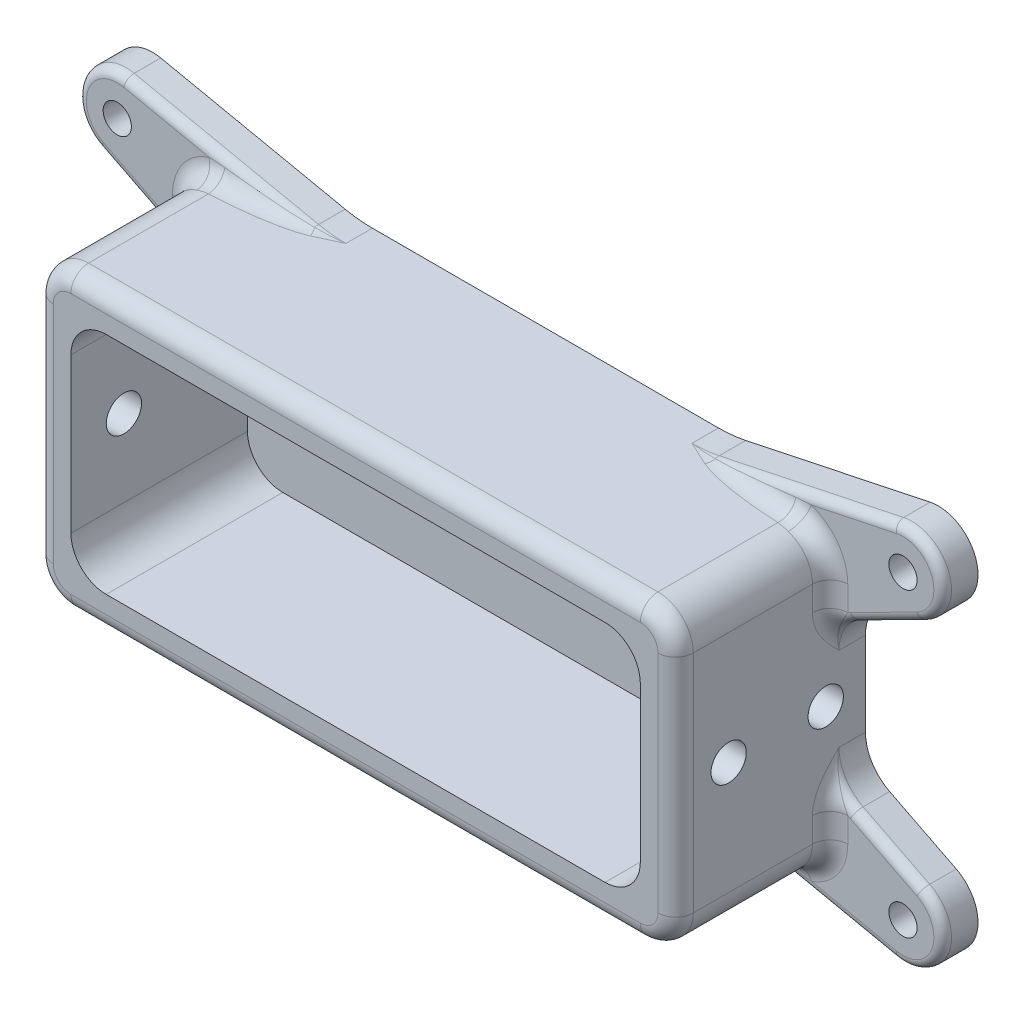
SolidWorks part; units mm, degrees
ref_plane "Спереди" through (0, 0, 0) normal (0, 0, 1) x (1, 0, 0)
ref_plane "Сверху" through (0, 0, 0) normal (0, 1, 0) x (1, 0, 0)
ref_plane "Справа" through (0, 0, 0) normal (1, 0, 0) x (0, 0, -1)
sketch "Эскиз1" plane through (0, 0, 0) normal (0, 0, 1) x (1, 0, 0)
  line L0 (0, 0) -> (50000, 0) construction
  line L1 (0, 0) -> (0, 50000) construction
  line L2 (-43.5744, 21.4603) -> (-21.1628, 16.75)
  line L3 (32.25, -12.75) -> (-32.25, -12.75)
  line L4 (32.25, -12.75) -> (32.25, 12.75)
  line L5 (32.25, 12.75) -> (-32.25, 12.75)
  line L6 (-32.25, -12.75) -> (-32.25, 12.75)
  line L7 (32.25, -12.75) -> (-32.25, 12.75) construction
  line L8 (32.25, 12.75) -> (-32.25, -12.75) construction
  line L9 (-21.1628, 16.75) -> (21.1628, 16.75)
  line L12 (-46.5338, 13.0423) -> (-36.25, 7.832)
  line L13 (-36.25, 7.832) -> (-36.25, -7.832)
  line L14 (-44.5, 17.0565) -> (-32.25, 12.75) construction
  line L15 (-21.1628, -16.75) -> (21.1628, -16.75)
  line L16 (-43.5744, -21.4603) -> (-21.1628, -16.75)
  line L17 (-46.5338, -13.0423) -> (-36.25, -7.832)
  line L18 (43.5744, 21.4603) -> (21.1628, 16.75)
  line L19 (46.5338, 13.0423) -> (36.25, 7.832)
  line L20 (36.25, 7.832) -> (36.25, -7.832)
  line L21 (46.5338, -13.0423) -> (36.25, -7.832)
  line L22 (43.5744, -21.4603) -> (21.1628, -16.75)
  line L23 (-36.25, 7.832) -> (-36.25, 16.75)
  line L24 (-36.25, 16.75) -> (-21.1628, 16.75)
  line L25 (-36.25, -7.832) -> (-36.25, -16.75)
  line L26 (-36.25, -16.75) -> (-21.1628, -16.75)
  line L27 (36.25, 7.832) -> (36.25, 16.75)
  line L28 (36.25, 16.75) -> (21.1628, 16.75)
  line L29 (36.25, -7.832) -> (36.25, -16.75)
  line L30 (36.25, -16.75) -> (21.1628, -16.75)
  circle A0 centre (-44.5, 17.0565) radius 1.6
  circle A1 centre (-44.5, -17.0565) radius 1.6
  circle A2 centre (44.5, 17.0565) radius 1.6
  circle A3 centre (44.5, -17.0565) radius 1.6
  arc A4 (-43.5744, 21.4603) -> (-46.5338, 13.0423) centre (-44.5, 17.0565) ccw
  arc A5 (-43.5744, -21.4603) -> (-46.5338, -13.0423) centre (-44.5, -17.0565) cw
  arc A6 (43.5744, 21.4603) -> (46.5338, 13.0423) centre (44.5, 17.0565) cw
  arc A7 (43.5744, -21.4603) -> (46.5338, -13.0423) centre (44.5, -17.0565) ccw
  point P14 (0, 0)
  dimension "D1" = 3.2
  dimension "D2" = 64.5
  dimension "D3" = 25.5
  dimension "D4" = 4
  dimension "D5" = 4
  dimension "D6" = 15
extrude "Бобышка-Вытянуть1" add sketch "Эскиз1" along normal blind 1.5 contours L22 A7 L21 L20 L19 A6 L18 L9 L2 A4 L12 L13 L17 A5 L16 L15 A2 L3 L6 L5 L4 A0 A1 A3 | L6 L3 L4 L5 | L2 A4 L12 L23 L24 A0 | A5 L16 L26 L25 L17 A1 | L22 A7 L21 L29 L30 A3 | A6 L18 L28 L27 L19 A2 region at (-39.8492, 16.0291, 0) region at (0, 15.9513, 0) region at (39.8492, 16.0291, 0) region at (-39.8492, -16.0291, 0) region at (39.8492, -16.0291, 0) region at (0, 0, 0)
extrude "Бобышка-Вытянуть2" add sketch "Эскиз1<3>" along normal blind 4 contours L22 A7 L21 L20 L19 A6 L18 L9 L2 A4 L12 L13 L17 A5 L16 L15 A2 L3 L6 L5 L4 A0 A1 A3 | L2 A4 L12 L23 L24 A0 | A5 L16 L26 L25 L17 A1 | L22 A7 L21 L29 L30 A3 | A6 L18 L28 L27 L19 A2 region at (-39.8492, 16.0291, 0) region at (0, 15.9513, 0) region at (39.8492, 16.0291, 0) region at (-39.8492, -16.0291, 0) region at (39.8492, -16.0291, 0)
sketch "Эскиз1<3>" plane through (0, 0, 0) normal (0, 0, 1) x (1, 0, 0) same geometry as "Эскиз1"
extrude "Бобышка-Вытянуть4" add sketch "Эскиз1<4>" along normal blind 20 from surface contours L30 L29 L20 L27 L28 L9 L24 L23 L13 L25 L26 L15 L3 L6 L5 L4 region at (0, 15.9513, 0) starting at face at (0, 0, 1.5)
sketch "Эскиз1<4>" plane through (0, 0, 0) normal (0, 0, 1) x (1, 0, 0) same geometry as "Эскиз1"
fillet "Скругление1" radius 15 4 edges at (21.1628, 16.75, 2) (-21.1628, 16.75, 2) (21.1628, -16.75, 2) (-21.1628, -16.75, 2)
fillet "Скругление2" radius 5 4 edges at (36.25, 7.832, 2) (36.25, -7.832, 2) (-36.25, -7.832, 2) (-36.25, 7.832, 2)
fillet "Скругление4" radius 4 8 edges at (-32.25, -12.75, 11.5) (-32.25, 12.75, 11.5) (32.25, 12.75, 11.5) (32.25, -12.75, 11.5) (36.25, -16.75, 12.75) (-36.25, -16.75, 12.75) (-36.25, 16.75, 12.75) (36.25, 16.75, 12.75)
fillet "Скругление6" radius 1 20 edges at (36.9898, 7.3775, 4) (21.1545, 16.8304, 4) (33.1316, 19.2655, 4) (48.7453, 18.549, 4) (21.1545, -16.8304, 4) (36.9898, -7.3775, 4) (42.762, -11.1313, 4) (48.7453, -18.549, 4) (-36.9898, -7.3775, 4) (-21.1545, -16.8304, 4) (-33.1316, -19.2655, 4) (-48.7453, -18.549, 4) (-36.9898, 7.3775, 4) (-21.1545, 16.8304, 4) (-33.1316, 19.2655, 4) (-48.7453, 18.549, 4) (42.762, 11.1313, 4) (33.1316, -19.2655, 4) (-42.762, -11.1313, 4) (-42.762, 11.1313, 4)
fillet "Скругление5" radius 2 32 edges at (-35.0784, 15.5784, 21.5) (0, 16.75, 21.5) (35.0784, 15.5784, 21.5) (36.25, 0, 21.5) (35.0784, -15.5784, 21.5) (0, -16.75, 21.5) (-35.0784, -15.5784, 21.5) (-29.1374, 16.75, 4) (-35.0784, 15.5784, 4) (-36.25, -10.4134, 4) (-35.0784, -15.5784, 4) (29.1374, -16.75, 4) (35.0784, -15.5784, 4) (36.25, 10.4134, 4) (35.0784, 15.5784, 4) (-36.25, 0, 21.5) (-36.25, 10.4134, 4) (-29.1374, -16.75, 4) (36.25, -10.4134, 4) (29.1374, 16.75, 4) (-36.25, 6.6352, 3.7513) (-20.8027, 16.75, 3.3057) (-24.2727, 16.75, 3.9328) (-20.8027, -16.75, 3.3057) (-24.2727, -16.75, 3.9328) (-36.25, -6.6352, 3.7513) (36.25, -6.6352, 3.7513) (20.8027, -16.75, 3.3057) (24.2727, -16.75, 3.9328) (36.25, 6.6352, 3.7513) (20.8027, 16.75, 3.3057) (24.2727, 16.75, 3.9328)
sketch "Эскиз2" plane through (0, 0, 0) normal (0, 0, -1) x (-1, 0, 0)
  line L0 (0, 0.8106) -> (0, -49999.1894) construction
  line L1 (0, 0) -> (-50000, 0) construction
  line L2 (-26, 9) -> (-29, 9)
  line L3 (26, 9) -> (29, 9)
  line L4 (26, 9) -> (26, -9)
  line L5 (26, -9) -> (29, -9)
  line L6 (29, 9) -> (29, -9)
  line L7 (26, 9) -> (29, -9) construction
  line L8 (26, -9) -> (29, 9) construction
  line L9 (-26, 9) -> (-26, -9)
  line L10 (-26, -9) -> (-29, -9)
  line L11 (-29, 9) -> (-29, -9)
  line L12 (-26, -9) -> (-29, 9) construction
  point P5 (27.5, 0)
  point P10 (-27.5, 0)
  dimension "D1" = 3
  dimension "D2" = 18
  dimension "D3" = 55
extrude "Вырез-Вытянуть1" cut sketch "Эскиз2" against normal offset from surface (1 mm away) 0.5 up to face at (0, 0, 1.5)
fillet "Скругление7" radius 1 8 edges at (29, -9, 0.5) (26, -9, 0.5) (26, 9, 0.5) (29, 9, 0.5) (-26, -9, 0.5) (-29, 9, 0.5) (-26, 9, 0.5) (-29, -9, 0.5)
sketch "Эскиз3" plane through (0, 0, 1.5) normal (0, 0, 1) x (1, 0, 0)
  line L0 (-21.0185, 1.8928) -> (21.0185, 1.8928) construction
  line L1 (0, 0) -> (0, 50000) construction
  text T0 "<b>Банка</b>\r\n<b>Design by ilust</b>" font "GOST type A_SW" height 4
  point P4 (0, 0)
  point P6 (0, 1.8928)
extrude "Вырез-Вытянуть2" cut sketch "Эскиз3" against normal blind 0.5
sketch "Эскиз4" plane through (-36.25, 0, 0) normal (-1, 0, 0) x (0, 0, 1)
  line L0 (0, 0) -> (50000, 0) construction
  line L1 (1.5, 8.75) -> (1.5, -8.75) construction
  circle A0 centre (4.5, 0) radius 2
  circle A1 centre (15.5, 0) radius 2
  point P7 (4.545, 0)
  dimension "D1" = 4
  dimension "D2" = 11
  dimension "D3" = 3
extrude "Вырез-Вытянуть3" cut sketch "Эскиз4" against normal through all
